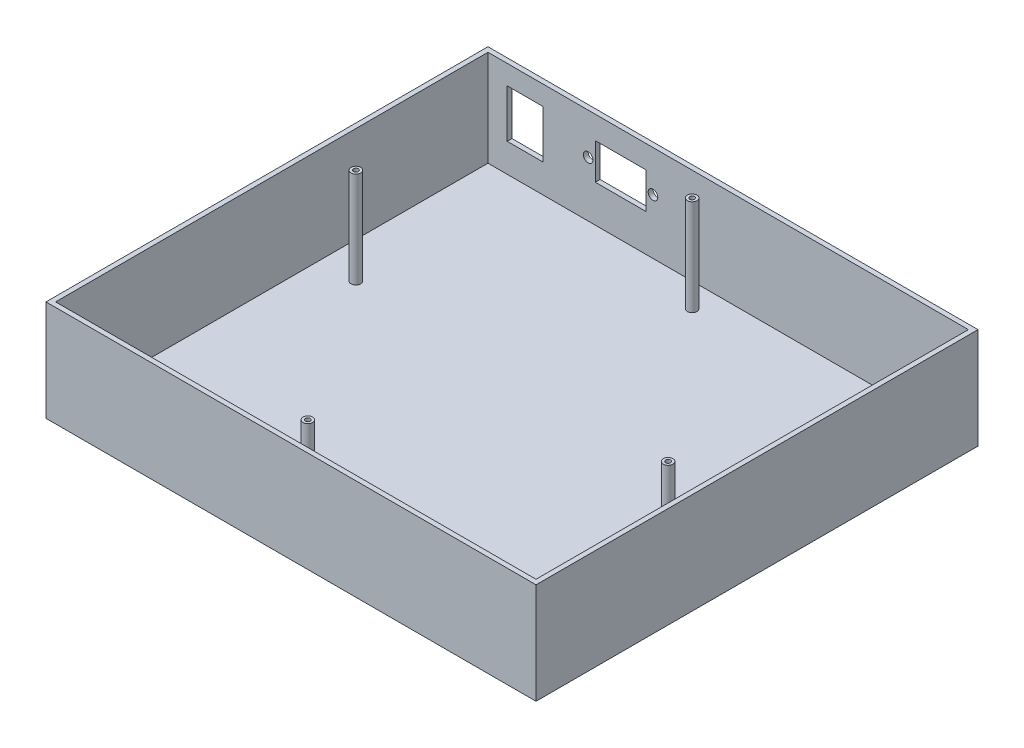
SolidWorks part; units mm, degrees
ref_plane "Front Plane" through (0, 0, 0) normal (0, 0, 1) x (1, 0, 0)
ref_plane "Top Plane" through (0, 0, 0) normal (0, 1, 0) x (1, 0, 0)
ref_plane "Right Plane" through (0, 0, 0) normal (1, 0, 0) x (0, 0, -1)
sketch "Sketch4" plane through (0, 0, 0) normal (0, 1, 0) x (1, 0, 0)
  line L1 (-100, 90) -> (100, 90)
  line L2 (-100, 90) -> (-100, -90)
  line L3 (-100, -90) -> (100, -90)
  line L4 (100, 90) -> (100, -90)
  line L5 (-100, 90) -> (100, -90) construction
  line L6 (-100, -90) -> (100, 90) construction
  line L7 (-102, 92) -> (102, 92)
  line L8 (-102, 92) -> (-102, -92)
  line L9 (-102, -92) -> (102, -92)
  line L10 (102, 92) -> (102, -92)
  line L11 (-102, 92) -> (102, -92) construction
  line L12 (-102, -92) -> (102, 92) construction
  point P0 (0, 0)
  point P6 (0, 0)
extrude "Boss-Extrude3" add sketch "Sketch4" along normal blind 2 contours L2 L1 L4 L3
extrude "Boss-Extrude4" add sketch "Sketch4<3>" along normal blind 42
sketch "Sketch4<3>" plane through (0, 0, 0) normal (0, 1, 0) x (1, 0, 0) same geometry as "Sketch4"
sketch "Sketch5" plane through (0, 0, -92) normal (0, 0, -1) x (-1, 0, 0)
  line L0 (102, 42) -> (102, 0) construction
  line L1 (77, 33.8937) -> (92, 33.8937)
  line L2 (77, 33.8937) -> (77, 13.8937)
  line L3 (77, 13.8937) -> (92, 13.8937)
  line L4 (92, 33.8937) -> (92, 13.8937)
  line L5 (77, 33.8937) -> (92, 13.8937) construction
  line L6 (77, 13.8937) -> (92, 33.8937) construction
  line L8 (34.3114, 32.4787) -> (55.3114, 32.4787)
  line L9 (34.3114, 32.4787) -> (34.3114, 17.4787)
  line L10 (34.3114, 17.4787) -> (55.3114, 17.4787)
  line L11 (55.3114, 32.4787) -> (55.3114, 17.4787)
  line L12 (34.3114, 32.4787) -> (55.3114, 17.4787) construction
  line L13 (34.3114, 17.4787) -> (55.3114, 32.4787) construction
  circle A0 centre (58.3114, 24.9787) radius 2
  circle A1 centre (31.3114, 24.9787) radius 2
  point P0 (84.5, 23.8937)
  point P7 (44.8114, 24.9787)
  dimension "D2" = 3
  dimension "D1" = 17.5
  dimension "D3" = 3
sketch "Sketch6" plane through (0, 2, 0) normal (0, 1, 0) x (1, 0, 0)
  line L0 (-100, 90) -> (-100, -90) construction
  line L1 (-100, -90) -> (100, -90) construction
  line L2 (-100, 0) -> (100, 0) construction
  line L3 (100, 90) -> (100, -90) construction
  line L4 (-100, 90) -> (100, 90) construction
  circle A0 centre (-5, -80) radius 2
  circle A1 centre (-5, 80) radius 2
  circle A2 centre (85, -20) radius 2
  circle A3 centre (-85, 20) radius 2
  dimension "D1" = 95
  dimension "D3" = 70
  dimension "D5" = 15
  dimension "D2" = 10
  dimension "D4" = 15
  dimension "D6" = 70
extrude "Boss-Extrude5" add sketch "Sketch6" along normal blind 40
sketch "Sketch8" plane through (0, 42, 0) normal (0, 1, 0) x (1, 0, 0)
  circle A0 centre (-5, 80) radius 1
  circle A1 centre (85, -20) radius 1
  circle A2 centre (-5, -80) radius 1
  circle A3 centre (-85, 20) radius 1
extrude "Cut-Extrude1" cut sketch "Sketch8" against normal blind 40
extrude "Cut-Extrude2" cut sketch "Sketch5" against normal blind 2
